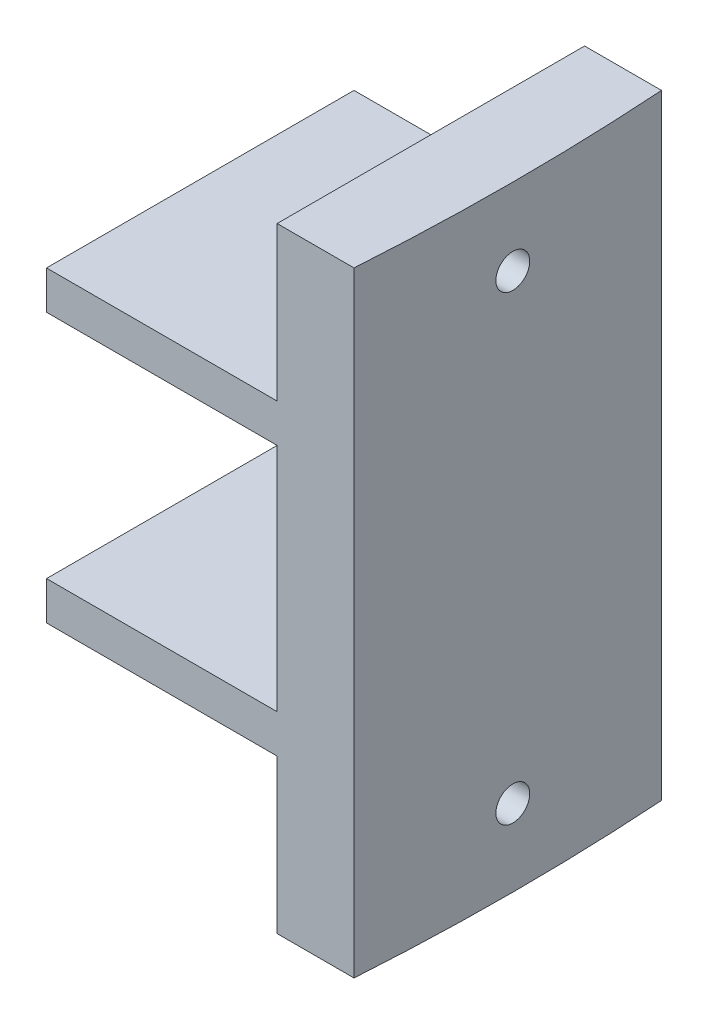
SolidWorks part; units mm, degrees
ref_plane "Front Plane" through (0, 0, 0) normal (0, 0, 1) x (1, 0, 0)
ref_plane "Top Plane" through (0, 0, 0) normal (0, 1, 0) x (1, 0, 0)
ref_plane "Right Plane" through (0, 0, 0) normal (1, 0, 0) x (0, 0, -1)
sketch "Sketch1" plane through (0, 0, 0) normal (0, 1, 0) x (1, 0, 0)
  line L0 (82.3381, 0) -> (88.6881, 0) construction
  line L1 (82.3381, -6.35) -> (95.0381, -6.35)
  line L3 (82.3381, 6.35) -> (95.0381, 6.35)
  line L7 (95.0381, 6.35) -> (82.3381, 6.35)
  line L8 (95.0381, 6.35) -> (95.0381, 4.6501)
  line L9 (95.0381, -6.35) -> (82.3381, -6.35)
  line L10 (82.3381, 6.35) -> (82.3381, -6.35)
  line L11 (82.3381, 3.7178) -> (95.1361, 4.6573) construction
  line L12 (82.3381, -3.7178) -> (95.1193, -4.9877) construction
  arc A0 (95.0381, -6.35) -> (95.0381, 6.35) centre (0, 0) ccw
  circle A1 centre (88.6881, 0) radius 1.1303
  dimension "D1" = 190.5
  dimension "D5" = 2.2606
  dimension "D6" = 88.6881
  dimension "D2" = 12.7
  dimension "D3" = 12.7
  dimension "D4" = 6.35
extrude "Boss-Extrude1" add sketch "Sketch1" along normal blind 12.7 contours L3 L10 L1 L8 A1 region at (82.5192, 0, 0)
sketch "Sketch2" plane through (0, 0, 6.35) normal (0, 0, 1) x (1, 0, 0)
  line L1 (82.3381, 1.5875) -> (91.8631, 1.5875)
  line L3 (82.3381, 11.1125) -> (91.8631, 11.1125)
  line L4 (82.3381, 0) -> (95.0381, 0)
  line L5 (95.0381, 0) -> (95.0381, 12.7)
  line L6 (95.0381, 12.7) -> (82.3381, 12.7)
  line L7 (82.3381, 12.7) -> (82.3381, 0)
  line L11 (82.3381, 11.1125) -> (82.3381, 1.5875)
  line L12 (91.8631, 1.5875) -> (91.8631, 11.1125)
  line L13 (82.3381, 6.35) -> (91.8631, 11.1125) construction
  line L14 (82.3381, 6.35) -> (91.8631, 1.5875) construction
  point P2 (82.3381, 6.35)
  dimension "D2" = 9.525
  dimension "D3" = 9.525
  dimension "D1" = 0
extrude "Cut-Extrude1" cut sketch "Sketch2" against normal through all
sketch "Sketch3" plane through (0, 12.7, 0) normal (0, 1, 0) x (1, 0, 0)
  line L0 (82.3381, -6.35) -> (95.0381, -6.35) construction
  line L1 (95.0381, 6.35) -> (82.3381, 6.35) construction
  line L7 (91.8631, -6.35) -> (95.0381, -6.35)
  line L8 (95.0381, 6.35) -> (91.8631, 6.35)
  line L13 (91.8631, 6.35) -> (91.8631, -6.35)
  arc A0 (95.0381, -6.35) -> (95.0381, 6.35) centre (0, 0) ccw construction
  arc A1 (95.0381, -6.35) -> (95.0381, 6.35) centre (0, 0) ccw
  dimension "D1" = 3.175
extrude "Boss-Extrude2" add sketch "Sketch3" along normal blind 6.35 and the other way blind 19.05
sketch "Sketch5" plane through (91.8631, 0, 0) normal (-1, 0, 0) x (0, 0, 1)
  line L0 (6.35, 0) -> (-6.35, 0) construction
  line L1 (-6.35, 0) -> (-6.35, -6.35) construction
  line L2 (-6.35, -6.35) -> (6.35, -6.35) construction
  line L3 (6.35, -6.35) -> (6.35, 0) construction
  line L4 (-6.35, 19.05) -> (-6.35, 12.7) construction
  line L5 (-6.35, 12.7) -> (6.35, 12.7) construction
  line L6 (6.35, 12.7) -> (6.35, 19.05) construction
  line L7 (6.35, 19.05) -> (-6.35, 19.05) construction
  line L8 (6.35, 0) -> (-6.35, 0) construction
  line L9 (-6.35, 0) -> (-6.35, -6.35) construction
  line L10 (-6.35, -6.35) -> (6.35, -6.35) construction
  line L11 (6.35, -6.35) -> (6.35, 0) construction
  line L12 (-6.35, 19.05) -> (-6.35, 12.7) construction
  line L13 (-6.35, 12.7) -> (6.35, 12.7) construction
  line L14 (6.35, 12.7) -> (6.35, 19.05) construction
  line L15 (6.35, 19.05) -> (-6.35, 19.05) construction
  line L16 (0, 19.05) -> (0, 12.7) construction
  line L17 (0, 0) -> (0, -6.35) construction
  circle A0 centre (0, 15.875) radius 0.6985
  circle A1 centre (0, -3.175) radius 0.6985
  dimension "D1" = 1.397
extrude "Cut-Extrude2" cut sketch "Sketch5" against normal through all
